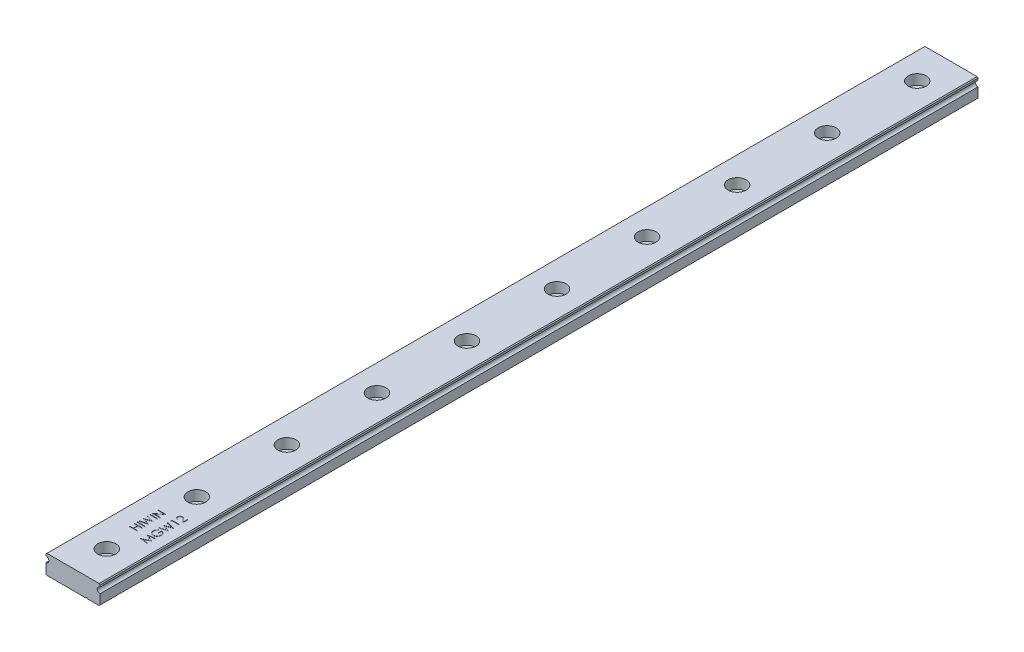
SolidWorks part; units mm, degrees
material "镀铬不锈钢"
ref_plane "前视基准面" through (0, 0, 0) normal (0, 0, 1) x (1, 0, 0)
ref_plane "上视基准面" through (0, 0, 0) normal (0, 1, 0) x (1, 0, 0)
ref_plane "右视基准面" through (0, 0, 0) normal (1, 0, 0) x (0, 0, -1)
sketch "草图1" plane through (0, 0, 0) normal (0, 0, 1) x (1, 0, 0)
  line L12 (-11.6, 8.5) -> (-12, 8.1)
  line L13 (12, 8.1) -> (11.6, 8.5)
  line L14 (11.6, 0) -> (12, 0.4)
  line L15 (12, 7.25) -> (12, 8.1)
  line L16 (0, 8.5) -> (0, 0) construction
  line L17 (12, 0.4) -> (12, 4.75)
  line L18 (6.3, 0) -> (11.6, 0)
  line L19 (-12, 0.4) -> (-11.6, 0)
  line L20 (-12, 8.1) -> (-12, 7.25)
  line L21 (-11.6, 0) -> (5.7, 0)
  line L22 (11.6, 8.5) -> (-11.6, 8.5)
  line L23 (-12, 4.75) -> (-12, 0.4)
  arc A3 (-12, 4.75) -> (-12, 7.25) centre (-12, 6) ccw
  arc A4 (6.3, 0) -> (5.7, 0) centre (6, 0) ccw
  arc A5 (12, 7.25) -> (12, 4.75) centre (12, 6) ccw
extrude "凸台-拉伸1" add sketch "草图1" against normal blind 390
hole_wizard "M4 六角凹头螺钉的柱形沉头孔1" positions "草图3" profile "草图2" counterbore size "M4" standard "ISO" end condition through all
sketch "草图3" plane through (-2.1754, 8.5, -52.9752) normal (0, 1, 0) x (-1, 0, 0)
  line L4 (-13.7754, 52.9752) -> (9.4246, 52.9752) construction
  point P15 (-2.1754, 37.9752)
  dimension "D1" = 15
sketch "草图2" plane through (0, 8.5, -15) normal (1, 0, 0) x (0, 0, 1)
  line L0 (0, 0) -> (0, 8.5)
  line L1 (0, 8.5) -> (2.25, 8.5)
  line L3 (2.25, 8.5) -> (2.25, 4.5)
  line L4 (2.25, 4.5) -> (4, 4.5)
  line L5 (4, 4.5) -> (4, 0)
  line L7 (4, 0) -> (0, 0)
  line L11 (0, -6.35) -> (0, 107.95) construction
  dimension "通孔孔直径" = 4.5
  dimension "通孔孔深度" = 8.5
  dimension "柱形沉头孔直径" = 8
  dimension "柱形沉头孔深度" = 4.5
pattern_linear "阵列(线性)1" count 10 spacing 40 along (0, 0, -1) of "M4 六角凹头螺钉的柱形沉头孔1"
sketch "草图4" plane through (0, 8.5, 0) normal (0, 1, 0) x (1, 0, 0)
  line L2 (0, 15) -> (0, 55) construction
  text T0 "HIWIN\r\nMGW12"
extrude "切除-拉伸1" cut sketch "草图4" against normal blind 0.1
equation "\"D1@凸台-拉伸1\" = 2 * \"D1@草图3\" + \"D3@阵列(线性)1\" *  (\"D1@阵列(线性)1\" - 1  ) "
